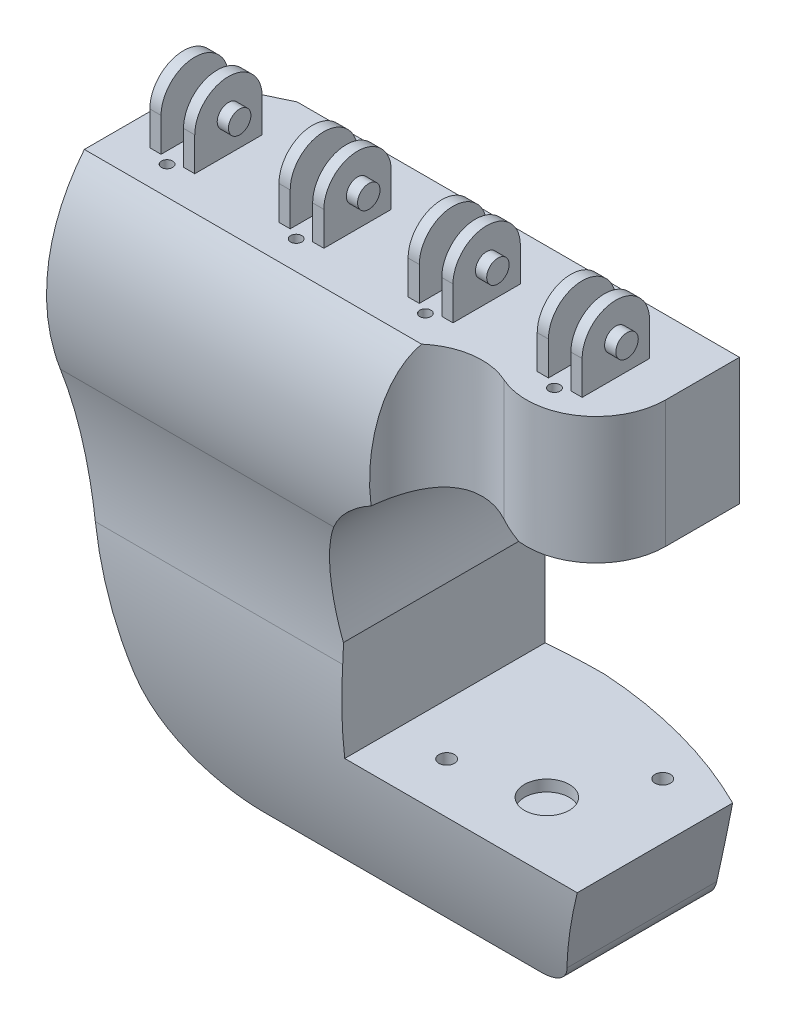
SolidWorks part; units mm, degrees
material "ABS"
ref_plane "Front Plane" through (0, 0, 0) normal (0, 0, 1) x (1, 0, 0)
ref_plane "Top Plane" through (0, 0, 0) normal (0, 1, 0) x (1, 0, 0)
ref_plane "Right Plane" through (0, 0, 0) normal (1, 0, 0) x (0, 0, -1)
sketch "Sketch1" plane through (0, 0, 0) normal (0, 0, 1) x (1, 0, 0)
  line L1 (0, 152.4) -> (152.4, 152.4)
  line L2 (0, 152.4) -> (0, 0)
  line L3 (0, 0) -> (152.4, 0)
  line L4 (152.4, 152.4) -> (152.4, 0)
  dimension "D1" = 152.4
extrude "Boss-Extrude1" add sketch "Sketch1" along normal blind 76.2
sketch "Sketch3" plane through (0, 0, 76.2) normal (0, 0, 1) x (1, 0, 0)
  line L0 (82.1057, 44.444) -> (82.1057, 64.764) construction
  line L1 (82.1057, 44.444) -> (132.9057, 44.444) construction
  line L2 (131.4198, 41.904) -> (124.7698, 21.6807)
  line L5 (117.6657, 100.324) -> (134.6523, 100.324) construction
  line L6 (136.9362, 101.6338) -> (140.9404, 108.4783) construction
  line L22 (132.9057, 44.444) -> (162.8642, 95.6522) construction
  line L25 (160.3111, 105.404) -> (150.6922, 111.0313) construction
  line L26 (134.6523, 102.9699) -> (117.029, 102.9699)
  line L27 (78.8231, 64.764) -> (78.8231, 41.904)
  line L28 (134.6523, 102.9699) -> (134.6523, 131.6857)
  line L29 (134.6523, 131.6857) -> (19.8317, 131.6857)
  line L32 (78.8231, 41.904) -> (131.4198, 41.904)
  line L35 (36.4349, 15.8356) -> (116.6948, 15.8356)
  arc A0 (82.1057, 64.764) -> (117.6657, 100.324) centre (117.6657, 64.764) cw construction
  arc A1 (134.6523, 100.324) -> (136.9362, 101.6338) centre (134.6523, 102.9699) ccw construction
  arc A2 (140.9404, 108.4783) -> (150.6922, 111.0313) centre (147.0928, 104.8789) cw construction
  arc A3 (162.8642, 95.6522) -> (160.3111, 105.404) centre (156.7118, 99.2515) ccw construction
  arc A5 (36.4349, 15.8356) -> (19.8317, 131.6857) centre (253.2648, 106.0257) cw
  arc A6 (116.6948, 15.8356) -> (124.7698, 21.6807) centre (116.6948, 24.336) ccw
  arc A7 (78.8231, 64.764) -> (117.029, 102.9699) centre (106.1956, 75.5974) cw
  point P10 (138.9383, 105.056)
  dimension "D1" = 60.96
  dimension "D2" = 120.329
  dimension "D3" = 55.88
  dimension "D4" = 20.32
  dimension "D5" = 25.4
  dimension "D6" = 2.54
  dimension "D7" = 57.1898
  dimension "D8" = 50.8
  dimension "D9" = 64.0343
  dimension "D10" = 6.5653
  dimension "D11" = 80.2598
  dimension "D12" = 115.8501
  dimension "D13" = 28.7158
extrude "Cut-Extrude1" cut sketch "Sketch3" against normal blind 101.6 flip side to cut
sketch "Sketch5" plane through (0, 131.6857, 0) normal (0, 1, 0) x (1, 0, 0)
  line L1 (134.6523, 0) -> (19.8317, 0) construction
  line L2 (0.3818, -50.973) -> (0.3818, -34.7763)
  line L4 (134.6523, 0) -> (134.6523, -76.2) construction
  line L6 (134.6523, -45.8213) -> (134.6523, -12.4474)
  arc A0 (0.3818, -34.7763) -> (91.6661, 0) centre (91.6661, -137.1945) cw
  arc A1 (91.6661, 0) -> (134.6523, -12.4474) centre (85.2451, -102.6231) cw
  arc A9 (134.6523, -45.8213) -> (0.3818, -50.973) centre (67.4182, -45.8213) cw
extrude "Cut-Extrude2" cut sketch "Sketch5" against normal blind 178.816 flip side to cut
sketch "Sketch6" plane through (134.6523, 0, 0) normal (1, 0, 0) x (0, 0, -1)
  line L0 (-12.4474, 131.6857) -> (-45.8213, 131.6857)
  line L2 (-39.4975, 15.8356) -> (-4.3735, 15.8356)
  line L3 (-4.3735, 15.8356) -> (-13.084, -73.8763)
  line L4 (-13.084, -73.8763) -> (-142.7408, -65.9445)
  line L5 (-142.7408, -65.9445) -> (-120.0056, 200.4017)
  line L6 (-120.0056, 200.4017) -> (3.7687, 197.9585)
  line L9 (-4.727, 15.8356) -> (-76.2, 15.8356) construction
  line L10 (0, 15.8356) -> (0, 41.904) construction
  line L11 (-0.6025, 41.904) -> (-76.2, 41.904) construction
  line L12 (0, 41.904) -> (3.7687, 197.9585)
  arc A0 (-45.8213, 131.6857) -> (-50.3497, 90.4658) centre (-4.1347, 106.2473) ccw
  arc A1 (-50.3497, 90.4658) -> (-46.364, 60.554) centre (-123.4482, 65.5041) cw
  arc A2 (-46.364, 60.554) -> (-39.4975, 15.8356) centre (58.732, 53.8051) ccw
  arc A3 (-12.4474, 131.6857) -> (0, 41.904) centre (-368.2705, 36.6003) cw
extrude "Cut-Extrude4" cut sketch "Sketch6" against normal blind 178.816
sketch "Sketch16" plane through (0, 131.6857, 0) normal (0, 1, 0) x (1, 0, 0)
  line L3 (134.6523, -12.4474) -> (134.6523, -45.8213) construction
  line L4 (170.8957, -71.7893) -> (168.1749, -1.2953)
  line L5 (18.4257, -52.97) -> (134.2712, -52.97) construction
  line L6 (134.6523, -29.1344) -> (168.1749, -1.2953)
  arc A0 (134.6523, -29.1344) -> (112.3806, -43.4706) centre (118.9024, -29.1344) cw
  arc A1 (112.3806, -43.4706) -> (91.5076, -52.97) centre (106.0829, -57.3145) ccw
  arc A2 (91.5076, -52.97) -> (170.8957, -71.7893) centre (140.8088, -21.8525) ccw
extrude "Cut-Extrude12" cut sketch "Sketch16" against normal blind 44.196
fillet "Fillet2" radius 25.4 1 edges at (36.4349, 15.8356, 25.553)
shell "Shell2" thickness 2.54 removed face at (111.6889, 27.276, 4.1603) removed face at (58.0971, 57.45, 6.8447) removed face at (92.4887, 105.7847, 7.3134) removed face at (132.3159, 117.3278, 11.2807)
sketch "Sketch8" plane through (0, 131.6857, 0) normal (0, 1, 0) x (1, 0, 0)
  line L0 (26.9314, -38.1018) -> (26.9314, -22.8618)
  line L1 (26.9314, -38.1018) -> (29.4714, -38.1018)
  line L2 (26.9314, -22.8618) -> (29.4714, -22.8618)
  line L3 (29.4714, -38.1018) -> (29.4714, -22.8618)
  line L4 (34.5514, -38.1018) -> (34.5514, -22.8618)
  line L5 (34.5514, -38.1018) -> (37.0914, -38.1018)
  line L6 (34.5514, -22.8618) -> (37.0914, -22.8618)
  line L7 (37.0914, -38.1018) -> (37.0914, -22.8618)
  dimension "D1" = 10.16
  dimension "D2" = 15.24
  dimension "D3" = 2.54
extrude "Boss-Extrude4" add sketch "Sketch8" along normal blind 15.24
sketch "Sketch10" plane through (26.9314, 0, 0) normal (-1, 0, 0) x (0, 0, 1)
  line L0 (22.8618, 139.3057) -> (22.8618, 156.9194)
  line L1 (22.8618, 146.9257) -> (22.8618, 131.6857) construction
  line L2 (22.8618, 156.9194) -> (45.9702, 156.9194)
  line L3 (45.9702, 156.9194) -> (38.1018, 139.3057)
  line L4 (38.1018, 146.9257) -> (38.1018, 131.6857) construction
  line L5 (22.8618, 146.9257) -> (38.1018, 146.9257) construction
  arc A0 (22.8618, 139.3057) -> (38.1018, 139.3057) centre (30.4818, 139.3057) cw
extrude "Cut-Extrude6" cut sketch "Sketch10" against normal blind 16.51
sketch "Sketch11" plane through (26.9314, 0, 0) normal (-1, 0, 0) x (0, 0, 1)
  line L1 (38.1018, 139.3057) -> (38.1018, 131.6857) construction
  circle A0 centre (30.4818, 139.3073) radius 2.54
  arc A1 (38.1018, 139.3057) -> (22.8618, 139.3057) centre (30.4818, 139.3057) ccw construction
  point P5 (30.4818, 146.9257)
  dimension "D1" = 7.62
  dimension "D3" = 5.08
  dimension "D2" = 7.6184
extrude "Boss-Extrude6" add sketch "Sketch11" along normal blind 2.54
sketch "Sketch12" plane through (37.0914, 0, 0) normal (1, 0, 0) x (0, 0, -1)
  line L0 (-38.1018, 139.3057) -> (-38.1018, 131.6857) construction
  line L1 (-38.1018, 131.6857) -> (-22.8618, 131.6857) construction
  circle A0 centre (-30.4818, 139.3057) radius 2.54
  dimension "D1" = 5.08
  dimension "D2" = 7.62
  dimension "D3" = 7.62
extrude "Boss-Extrude7" add sketch "Sketch12" along normal blind 2.54
sketch "Sketch13" plane through (0, 131.6857, 0) normal (0, 1, 0) x (1, 0, 0)
  line L0 (34.5514, -38.1018) -> (37.0914, -38.1018) construction
  circle A0 centre (32.1015, -39.3718) radius 1.27
  circle A1 centre (32.1015, -21.5918) radius 1.27
  dimension "D1" = 2.54
  dimension "D2" = 17.78
  dimension "D3" = 1.27
extrude "Cut-Extrude7" cut sketch "Sketch13" against normal blind 2.54
pattern_linear "LPattern2" count 4 spacing 29.21 along (1, 0, 0) of "Boss-Extrude4", "Cut-Extrude6", "Boss-Extrude6", "Boss-Extrude7", "Cut-Extrude7"
sketch "Sketch14" plane through (0, 41.904, 0) normal (0, 1, 0) x (1, 0, 0)
  line L0 (131.4198, -45.9059) -> (78.8231, -45.9059) construction
  line L1 (78.8231, -0.6025) -> (78.8231, -45.9059) construction
  circle A0 centre (109.3031, -30.6659) radius 5.08
  dimension "D1" = 15.24
  dimension "D2" = 30.48
extrude "Cut-Extrude8" cut sketch "Sketch14" against normal blind 2.54
ref_point "Point1"
sketch "Sketch15" plane through (0, 41.904, 0) normal (0, 1, 0) x (1, 0, 0)
  line L0 (90.4403, -34.4667) -> (118.7704, -13.9141) construction
  line L1 (109.3031, -30.6659) -> (104.6054, -24.1904) construction
  circle A0 centre (90.4403, -34.4667) radius 1.75
  circle A1 centre (118.7704, -13.9141) radius 1.75
  circle A3 centre (109.3031, -30.6659) radius 5.08 construction
  dimension "D2" = 3.5
  dimension "D3" = 8
  dimension "D1" = 35
  dimension "D4" = 17.5
extrude "Cut-Extrude9" cut sketch "Sketch15" against normal blind 2.54
sketch "Sketch19" plane through (0, 39.364, 0) normal (0, -1, 0) x (1, 0, 0)
  line L0 (113.5223, 13.3974) -> (116.7152, 11.0811)
  line L1 (120.8257, 16.7472) -> (117.6328, 19.0635)
  line L2 (95.6884, 34.9834) -> (92.4956, 37.2997)
  line L3 (88.3851, 31.6336) -> (91.5779, 29.3173)
  line L4 (92.4292, 17.2809) -> (89.9293, 13.835)
  line L5 (89.9293, 13.835) -> (99.3162, 7.0251)
  line L6 (99.3162, 7.0251) -> (101.8161, 10.4711)
  line L7 (99.6495, 4.9302) -> (87.8343, 13.5017)
  line L8 (87.8343, 13.5017) -> (90.6681, 17.4079)
  line L9 (89.7938, 28.7585) -> (87.5042, 30.4195)
  line L10 (99.6495, 4.9302) -> (102.4833, 8.8364)
  line L11 (113.5448, 11.528) -> (115.8343, 9.867)
  line L12 (121.7065, 17.9613) -> (119.4169, 19.6223)
  line L13 (95.6659, 36.8528) -> (93.3764, 38.5138)
  arc A0 (116.7152, 11.0811) -> (120.8257, 16.7472) centre (118.7704, 13.9141) ccw
  circle A1 centre (118.7704, 13.9141) radius 1.75 construction
  arc A2 (117.6328, 19.0635) -> (95.6884, 34.9834) centre (104.6054, 24.1904) ccw
  arc A3 (92.4956, 37.2997) -> (88.3851, 31.6336) centre (90.4403, 34.4667) ccw
  arc A4 (90.6681, 17.4079) -> (89.7938, 28.7585) centre (104.6054, 24.1904) cw
  circle A5 centre (90.4403, 34.4667) radius 1.75 construction
  arc A6 (91.5779, 29.3173) -> (92.4292, 17.2809) centre (104.6054, 24.1904) ccw
  arc A8 (113.5223, 13.3974) -> (101.8161, 10.4711) centre (104.6054, 24.1904) cw
  arc A9 (102.4833, 8.8364) -> (113.5448, 11.528) centre (104.6054, 24.1904) ccw
  arc A10 (115.8343, 9.867) -> (121.7065, 17.9613) centre (118.7704, 13.9141) ccw
  arc A11 (119.4169, 19.6223) -> (95.6659, 36.8528) centre (104.6054, 24.1904) ccw
  arc A12 (93.3764, 38.5138) -> (87.5042, 30.4195) centre (90.4403, 34.4667) ccw
  dimension "D2" = 17
  dimension "D4" = 14
  dimension "D5" = 15.5
  dimension "D8" = 5
  dimension "D1" = 7
  dimension "D3" = 4.2572
  dimension "D6" = 1.5
  dimension "D7" = 1.5
extrude "Boss-Extrude8" add sketch "Sketch19" along normal blind 1.5
sketch "Sketch21" plane through (0, 0, 38.1018) normal (0, 0, 1) x (1, 0, 0)
  line L0 (37.0958, 139.3002) -> (26.9314, 139.3057)
  dimension "D1" = 10.1643
